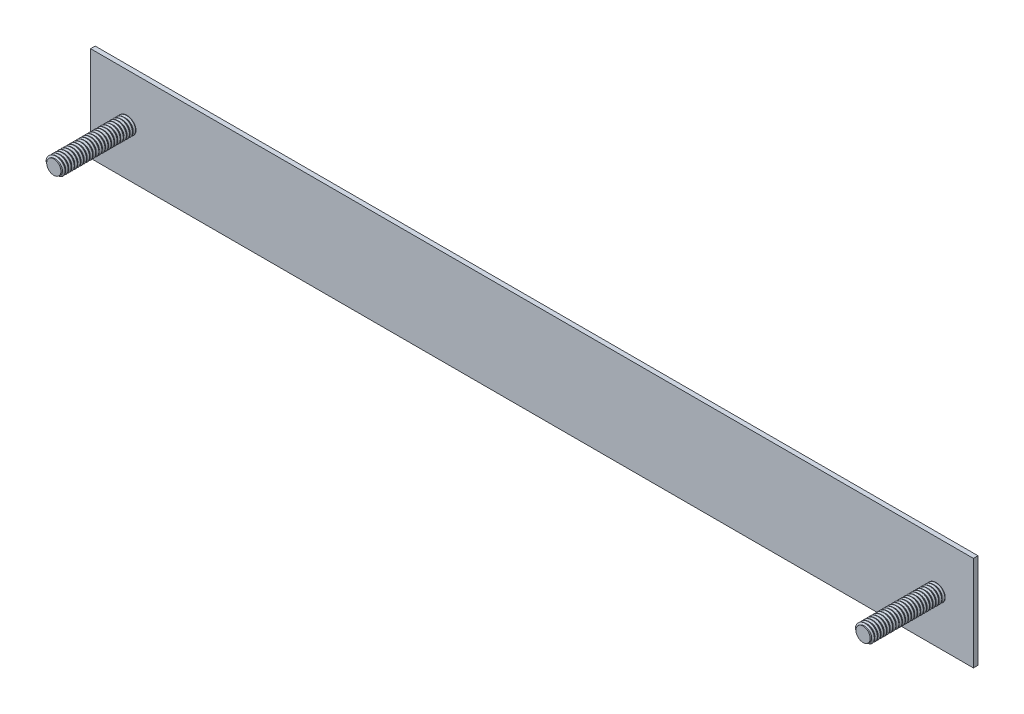
SolidWorks part; units mm, degrees
ref_plane "Front Plane" through (0, 0, 0) normal (0, 0, 1) x (1, 0, 0)
ref_plane "Top Plane" through (0, 0, 0) normal (0, 1, 0) x (1, 0, 0)
ref_plane "Right Plane" through (0, 0, 0) normal (1, 0, 0) x (0, 0, -1)
sketch "Sketch1" plane through (0, 0, 0) normal (0, 0, 1) x (1, 0, 0)
  line L1 (0, 0) -> (304.8, 0)
  line L2 (0, 0) -> (0, 32.766)
  line L3 (0, 32.766) -> (304.8, 32.766)
  line L4 (304.8, 0) -> (304.8, 32.766)
  dimension "D1" = 32.766
  dimension "D2" = 304.8
extrude "Boss-Extrude1" add sketch "Sketch1" along normal blind 1.5875
sketch "Sketch2" plane through (0, 0, 1.5875) normal (0, 0, 1) x (1, 0, 0)
  line L1 (0, 32.766) -> (0, 0) construction
  line L2 (304.8, 0) -> (304.8, 32.766) construction
  circle A0 centre (12.7, 16.4059) radius 2.4574
  circle A1 centre (292.1, 16.4059) radius 2.4574
  dimension "D1" = 4.9149
  dimension "D4" = 4.9149
  dimension "D2" = 16.4059
  dimension "D3" = 12.7
  dimension "D5" = 16.4059
  dimension "D6" = 12.7
extrude "Boss-Extrude2" add sketch "Sketch2" along normal blind 25.4
thread "Thread1" pitch 1.0583 method extrude profile "Thread Profile1" start angle 0, offset 0, length 0, pitch 1.0583, diameter 4.9149
ref_plane "Plane1" through (10.2425, 16.4059, 26.9875) normal (0, -1, 0) x (-1, 0, 0)
sketch "Thread Profile1" plane through (10.2425, 16.4059, 26.9875) normal (0, -1, 0) x (-1, 0, 0)
  line L0 (0, 0) -> (0, 1.0583) construction
  line L1 (0, 0) -> (0.5728, 0.3307)
  line L2 (0.5728, 0.3307) -> (0.5728, 0.463)
  line L3 (0.5728, 0.463) -> (0, 0.7937)
  line L4 (0.5728, 0.3969) -> (0, 0.3969) construction
  line L11 (0, 0) -> (0, 0.7937)
  point P2 (0, 0)
  dimension "Pitch" = 1.0583
  dimension "Profile_Angle" = 60
  dimension "Profile_Land" = 0.1323
  dimension "Profile_Height" = 0.5728
thread "Thread2" pitch 1.0583 method extrude profile "Thread Profile2" start angle 0, offset 0, length 0, pitch 1.0583, diameter 4.9149
ref_plane "Plane2" through (289.6426, 16.4059, 26.9875) normal (0, -1, 0) x (-1, 0, 0)
sketch "Thread Profile2" plane through (289.6426, 16.4059, 26.9875) normal (0, -1, 0) x (-1, 0, 0)
  line L0 (0, 0) -> (0, 1.0583) construction
  line L1 (0, 0) -> (0.5728, 0.3307)
  line L2 (0.5728, 0.3307) -> (0.5728, 0.463)
  line L3 (0.5728, 0.463) -> (0, 0.7937)
  line L4 (0.5728, 0.3969) -> (0, 0.3969) construction
  line L11 (0, 0) -> (0, 0.7937)
  point P2 (0, 0)
  dimension "Pitch" = 1.0583
  dimension "Profile_Angle" = 60
  dimension "Profile_Land" = 0.1323
  dimension "Profile_Height" = 0.5728
